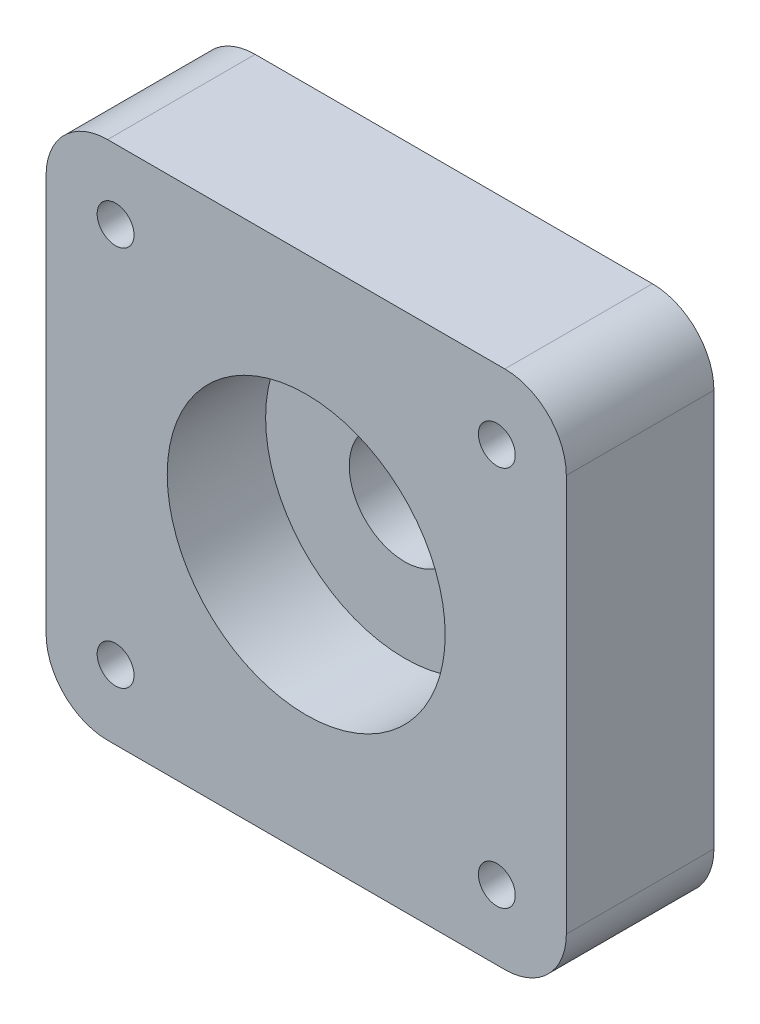
SolidWorks part; units mm, degrees
ref_plane "Alzado" through (0, 0, 0) normal (0, 0, 1) x (1, 0, 0)
ref_plane "Planta" through (0, 0, 0) normal (0, 1, 0) x (1, 0, 0)
ref_plane "Vista lateral" through (0, 0, 0) normal (1, 0, 0) x (0, 0, -1)
sketch "Croquis1" plane through (0, 0, 0) normal (0, 0, 1) x (1, 0, 0)
  line L0 (0, 25.4786) -> (0, -27.3465) construction
  line L1 (-21.15, -21.15) -> (21.15, -21.15)
  line L2 (-21.15, -21.15) -> (-21.15, 21.15)
  line L3 (-21.15, 21.15) -> (21.15, 21.15)
  line L4 (21.15, -21.15) -> (21.15, 21.15)
  line L5 (-21.15, -21.15) -> (21.15, 21.15) construction
  line L6 (-21.15, 21.15) -> (21.15, -21.15) construction
  line L7 (-15.5, 15.5) -> (-15.5, -15.5) construction
  line L8 (15.5, 15.5) -> (15.5, -15.5) construction
  circle A0 centre (-15.5, 15.5) radius 1.5
  circle A1 centre (-15.5, -15.5) radius 1.5
  circle A2 centre (15.5, -15.5) radius 1.5
  circle A3 centre (15.5, 15.5) radius 1.5
  point P0 (0, 0)
  dimension "D3" = 3
  dimension "D1" = 42.3
  dimension "D2" = 42.3
  dimension "D4" = 15.5
extrude "Saliente-Extruir1" add sketch "Croquis1" along normal mid plane 12
fillet "Redondeo1" radius 5 4 edges at (-21.15, 21.15, 0) (-21.15, -21.15, 0) (21.15, -21.15, 0) (21.15, 21.15, 0)
sketch "Croquis2" plane through (0, 0, 6) normal (0, 0, 1) x (1, 0, 0)
  circle A0 centre (0, 0) radius 11.3
  dimension "D1" = 22.6
extrude "Cortar-Extruir1" cut sketch "Croquis2" against normal blind 8
sketch "Croquis3" plane through (0, 0, -6) normal (0, 0, -1) x (-1, 0, 0)
  circle A0 centre (0, 0) radius 4.5
  dimension "D1" = 9
extrude "Cortar-Extruir2" cut sketch "Croquis3" against normal blind 10
